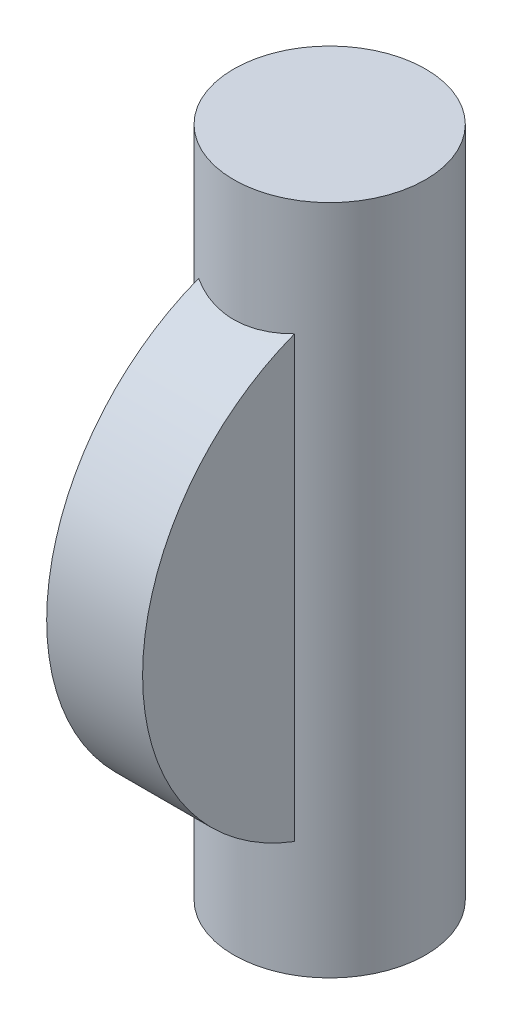
SolidWorks part; units mm, degrees
ref_plane "Front Plane" through (0, 0, 0) normal (0, 0, 1) x (1, 0, 0)
ref_plane "Top Plane" through (0, 0, 0) normal (0, 1, 0) x (1, 0, 0)
ref_plane "Right Plane" through (0, 0, 0) normal (1, 0, 0) x (0, 0, -1)
sketch "Sketch1" plane through (0, 0, 0) normal (0, 1, 0) x (1, 0, 0)
  circle A0 centre (0, 0) radius 2.54
  dimension "D1" = 5.08
extrude "Boss-Extrude1" add sketch "Sketch1" along normal blind 17.78
sketch "Sketch2" plane through (0, 0, 0) normal (1, 0, 0) x (0, 0, -1)
  line L0 (-2.54, 0) -> (2.54, 0) construction
  line L1 (0, 15.113) -> (0, 2.667)
  circle A0 centre (0, 8.89) radius 6.223
  dimension "D1" = 12.446
  dimension "D2" = 8.89
extrude "Boss-Extrude2" add sketch "Sketch2" along normal blind 1.27 and the other way blind 1.27 contours L1 A0 region at (0, 8.89, 2.6411)
